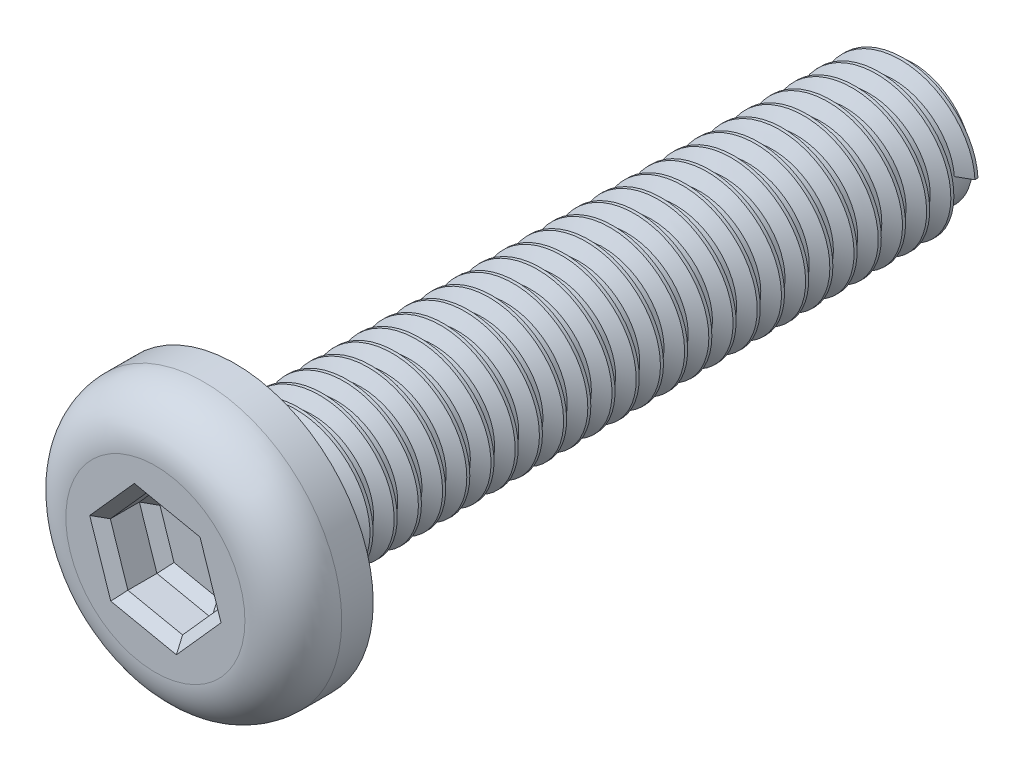
SolidWorks part; units mm, degrees
ref_plane "前视基准面" through (0, 0, 0) normal (0, 0, 1) x (1, 0, 0)
ref_plane "上视基准面" through (0, 0, 0) normal (0, 1, 0) x (1, 0, 0)
ref_plane "右视基准面" through (0, 0, 0) normal (1, 0, 0) x (0, 0, -1)
sketch "草图1" plane through (0, 0, 0) normal (0, 0, 1) x (1, 0, 0)
  circle A0 centre (0, 0) radius 2.85
  dimension "D1" = 5.7
extrude "凸台-拉伸1" add sketch "草图1" along normal blind 1.65
sketch "草图2" plane through (0, 0, 0) normal (0, 0, -1) x (-1, 0, 0)
  circle A0 centre (0, 0) radius 1.2295
  dimension "D1" = 2.459
extrude "凸台-拉伸2" add sketch "草图2" along normal blind 14
fillet "圆角1" radius 1 1 edges at (2.85, 0, 1.65)
sketch "草图3" plane through (0, 0, 1.65) normal (0, 0, 1) x (1, 0, 0)
  line L1 (0.3622, -1.0964) -> (1.1306, -0.2345)
  line L2 (1.1306, -0.2345) -> (0.7684, 0.8619)
  line L3 (0.7684, 0.8619) -> (-0.3622, 1.0964)
  line L4 (-0.3622, 1.0964) -> (-1.1306, 0.2345)
  line L5 (-1.1306, 0.2345) -> (-0.7684, -0.8619)
  line L6 (-0.7684, -0.8619) -> (0.3622, -1.0964)
  circle A0 centre (0, 0) radius 1 construction
  dimension "D1" = 2
extrude "切除-拉伸1" cut sketch "草图3" against normal blind 1
chamfer "倒角1" distance 0.2 angle 45 12 edges at (0.7464, -0.6655, 1.65) (0.9495, 0.3137, 1.65) (0.2031, 0.9792, 1.65) (-0.7464, 0.6655, 1.65) (-0.9495, -0.3137, 1.65) (-0.2031, -0.9792, 1.65) (-0.9495, -0.3137, 0.65) (-0.7464, 0.6655, 0.65) (0.2031, 0.9792, 0.65) (0.9495, 0.3137, 0.65) (0.7464, -0.6655, 0.65) (-0.2031, -0.9792, 0.65)
thread "螺纹线1" pitch 0.5 method extrude profile "螺纹线轮廓2" start angle 0, offset 0, length 0, pitch 0.5, diameter 2.459
ref_plane "基准面2" through (1.2295, 0, -14) normal (0, -1, 0) x (1, 0, 0)
sketch "螺纹线轮廓2" plane through (1.2295, 0, -14) normal (0, -1, 0) x (1, 0, 0)
  line L0 (0, 0) -> (0, 0.5) construction
  line L1 (0, 0) -> (0.2706, 0.1562)
  line L2 (0.2706, 0.1562) -> (0.2706, 0.2187)
  line L3 (0.2706, 0.2187) -> (0, 0.375)
  line L4 (0.2706, 0.1875) -> (0, 0.1875) construction
  line L11 (0, 0) -> (0, 0.375)
  point P2 (0, 0)
  dimension "Pitch" = 0.5
  dimension "Profile_Angle" = 60
  dimension "Profile_Land" = 0.0625
  dimension "Profile_Height" = 0.2706
